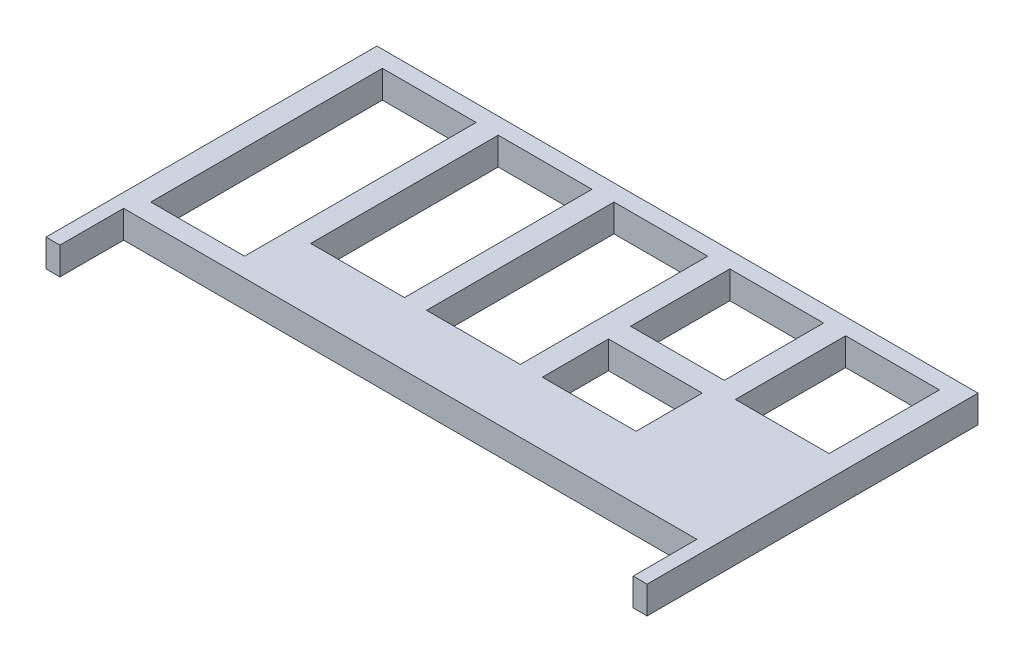
SolidWorks part; units mm, degrees
ref_plane "Front" through (0, 0, 0) normal (0, 0, 1) x (1, 0, 0)
ref_plane "Top" through (0, 0, 0) normal (0, 1, 0) x (1, 0, 0)
ref_plane "Right" through (0, 0, 0) normal (1, 0, 0) x (0, 0, -1)
sketch "Sketch1" plane through (0, 0, 0) normal (0, 1, 0) x (1, 0, 0)
  line L1 (-54.5, -30) -> (54.5, -30)
  line L2 (-54.5, -30) -> (-54.5, 30)
  line L3 (-54.5, 30) -> (54.5, 30)
  line L4 (54.5, -30) -> (54.5, 30)
  line L5 (-54.5, -30) -> (54.5, 30) construction
  line L6 (-54.5, 30) -> (54.5, -30) construction
  line L12 (12.5, 9) -> (29.5, 9)
  line L13 (-50.5, -15) -> (-33.5, -15)
  line L14 (-50.5, -15) -> (-50.5, 27)
  line L15 (-50.5, 27) -> (-33.5, 27)
  line L16 (-33.5, -15) -> (-33.5, 27)
  line L17 (-50.5, -15) -> (-33.5, 27) construction
  line L18 (-50.5, 27) -> (-33.5, -15) construction
  line L23 (12.5, 9) -> (12.5, 27)
  line L24 (12.5, 27) -> (29.5, 27)
  line L25 (-12.5, 27) -> (-29.5, 27)
  line L26 (-12.5, 27) -> (-12.5, -7)
  line L27 (-12.5, -7) -> (-29.5, -7)
  line L28 (-29.5, 27) -> (-29.5, -7)
  line L29 (-12.5, 27) -> (-29.5, -7) construction
  line L30 (-12.5, -7) -> (-29.5, 27) construction
  line L35 (29.5, 9) -> (29.5, 27)
  line L36 (12.5, 9) -> (29.5, 27) construction
  line L37 (-8.5, -7) -> (8.5, -7)
  line L38 (-8.5, -7) -> (-8.5, 27)
  line L39 (-8.5, 27) -> (8.5, 27)
  line L40 (8.5, -7) -> (8.5, 27)
  line L41 (-8.5, -7) -> (8.5, 27) construction
  line L42 (-8.5, 27) -> (8.5, -7) construction
  line L48 (12.5, 27) -> (29.5, 9) construction
  line L49 (33.5, 7) -> (50.5, 7)
  line L50 (33.5, 7) -> (33.5, 27)
  line L51 (33.5, 27) -> (50.5, 27)
  line L52 (50.5, 7) -> (50.5, 27)
  line L53 (33.5, 7) -> (50.5, 27) construction
  line L54 (33.5, 27) -> (50.5, 7) construction
  line L55 (12.5, 5) -> (29.5, 5)
  line L56 (12.5, 5) -> (12.5, -7)
  line L57 (12.5, -7) -> (29.5, -7)
  line L58 (29.5, 5) -> (29.5, -7)
  line L59 (12.5, 5) -> (29.5, -7) construction
  line L60 (12.5, -7) -> (29.5, 5) construction
  line L61 (51.975, -30) -> (54.5, -30)
  line L67 (-51.975, -30) -> (51.975, -30)
  line L68 (-51.975, -30) -> (-51.975, -18.45)
  line L69 (-51.975, -18.45) -> (51.975, -18.45)
  line L70 (51.975, -30) -> (51.975, -18.45)
  point P0 (0, 0)
  point P6 (42, 17)
  point P9 (21, 18)
  point P11 (-42, 6)
  point P21 (-21, 10)
  point P26 (21, -1)
  point P31 (0, 10)
  point P36 (0, 0)
  point P37 (0, 0)
  point P39 (0, 0)
  point P44 (0, 0)
  point P45 (55.1325, -30)
  dimension "D1" = 109
  dimension "D2" = 60
  dimension "D3" = 4
  dimension "D4" = 3
  dimension "D5" = 17
  dimension "D6" = 4
  dimension "D7" = 17
  dimension "D8" = 3
  dimension "D9" = 4
  dimension "D10" = 3
  dimension "D11" = 17
  dimension "D12" = 4
  dimension "D13" = 17
  dimension "D14" = 18
  dimension "D15" = 4
  dimension "D16" = 17
  dimension "D17" = 20
  dimension "D18" = 12
  dimension "D19" = 4
  dimension "D20" = 2.525
  dimension "D21" = 42
  dimension "D22" = 34
  dimension "D23" = 4
  dimension "D25" = 34
  dimension "D26" = 11.55
  dimension "D27" = 103.95
extrude "Boss-Extrude1" add sketch "Sketch1" along normal blind 5 contours L68 L69 L1 L4 L3 L2 L52 L49 L50 L51 L40 L37 L38 L39 L35 L12 L23 L24 L28 L25 L26 L27 L16 L13 L14 L15 L55 L58 L57 L56 region at (-53.2558, 0, 0)
